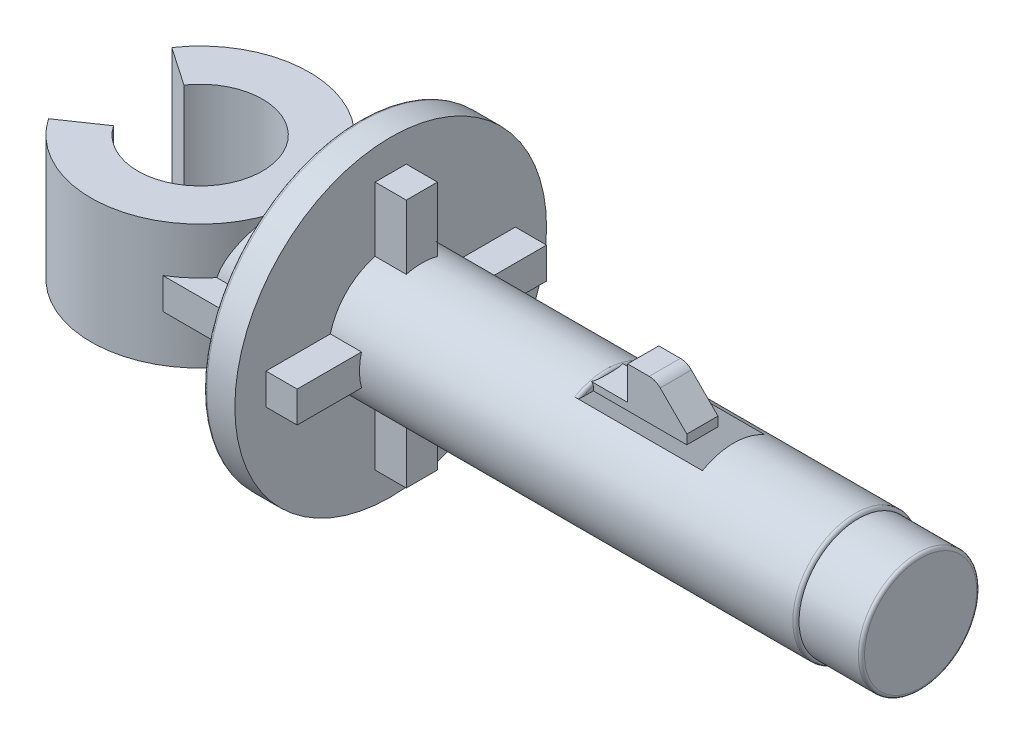
SolidWorks part; units mm, degrees
material "ABS PC"
ref_plane "Piano frontale" through (0, 0, 0) normal (0, 0, 1) x (1, 0, 0)
ref_plane "Piano superiore" through (0, 0, 0) normal (0, 1, 0) x (1, 0, 0)
ref_plane "Piano destro" through (0, 0, 0) normal (1, 0, 0) x (0, 0, -1)
sketch "Schizzo1" plane through (0, 0, 0) normal (1, 0, 0) x (0, 0, -1)
  circle A0 centre (0, 0) radius 2
  dimension "D1" = 4
extrude "Estrusione-Estrusione1" add sketch "Schizzo1" against normal blind 17
sketch "Schizzo2" plane through (0, 0, 0) normal (1, 0, 0) x (0, 0, -1)
  circle A0 centre (0, 0) radius 1.9
  dimension "D1" = 3.8
extrude "Taglio-Estrusione1" cut sketch "Schizzo2" against normal blind 2 flip side to cut
ref_plane "Piano1" through (0, -2, 0) normal (0, -1, 0) x (-1, 0, 0)
sketch "Schizzo6" plane through (0, -2, 0) normal (0, -1, 0) x (-1, 0, 0)
  line L1 (17, -2) -> (2, -2)
  line L2 (17, -2) -> (17, 2)
  line L3 (17, 2) -> (2, 2)
  line L4 (2, -2) -> (2, 2)
extrude "Taglio-Estrusione3" cut sketch "Schizzo6" against normal blind 0.1
ref_plane "Piano2" through (0, 2, 0) normal (0, 1, 0) x (1, 0, 0)
sketch "Schizzo5" plane through (0, 0, 0) normal (0, 1, 0) x (1, 0, 0)
  line L0 (-17, 2) -> (-17, -2) construction
  line L1 (-16, 1) -> (-3, 1)
  line L2 (-16, 1) -> (-16, -1)
  line L3 (-16, -1) -> (-3, -1)
  line L4 (-3, 1) -> (-3, -1)
  line L5 (-16, 1) -> (-3, -1) construction
  line L6 (-16, -1) -> (-3, 1) construction
  line L7 (-2, -2) -> (-2, 2) construction
  line L8 (-17, -2) -> (-2, -2) construction
  point P0 (-9.5, 0)
  dimension "D1" = 1
  dimension "D2" = 1
  dimension "D3" = 2
  dimension "D4" = 1
extrude "Taglio-Estrusione4" cut sketch "Schizzo5" against normal through all and the other way offset from surface 0.3 other way up to plane "Piano2"
sketch "Schizzo7" plane through (0, 2, 0) normal (0, 1, 0) x (1, 0, 0)
  line L0 (-10, 1) -> (-6, 1)
  line L1 (-6, 1) -> (-6, -1)
  line L2 (-6, -1) -> (-10, -1)
  line L9 (-2, 2) -> (-17, 2) construction
  line L10 (-17, -2) -> (-2, -2) construction
  line L11 (-10, 1) -> (-10, -1)
  line L12 (-2, -2) -> (-2, 2) construction
  dimension "D1" = 8
  dimension "D2" = 4
  dimension "D5" = 1
  dimension "D6" = 1
extrude "Taglio-Estrusione5" cut sketch "Schizzo7" against normal through all
ref_plane "Piano3" through (0, 1.7, 0) normal (0, 1, 0) x (1, 0, 0)
sketch "Schizzo12" plane through (0, 0, 0) normal (0, 0, 1) x (1, 0, 0)
  line L0 (-10, 2) -> (-8.9, 2)
  line L1 (-10, 1.7321) -> (-10, 2) construction
  line L2 (-8.9, 2) -> (-8.9, 3)
  line L3 (-8.9, 3) -> (-8, 3)
  line L4 (-8, 3) -> (-7, 2)
  line L5 (-7, 2) -> (-7, 1.7)
  line L6 (1.1, 1.7) -> (-1.1, 1.7) construction
  line L7 (-7, 1.7) -> (-10, 1.7)
  line L8 (-10, 1.7) -> (-10, 2)
  dimension "D1" = 3
  dimension "D2" = 1
  dimension "D3" = 0.3
  dimension "D4" = 0.9
  dimension "D5" = 45
  dimension "D6" = 0.3
extrude "Estrusione-Estrusione2" add sketch "Schizzo12" along normal mid plane 1
sketch "Schizzo16" plane through (0, 2, 0) normal (0, 1, 0) x (1, 0, 0)
  line L5 (-8.9, 0.5) -> (-10, 0.5)
  line L6 (-10, 0.5) -> (-10, 0)
  line L7 (-10, 0) -> (-10, -0.5)
  line L8 (-10, -0.5) -> (-8.9, -0.5)
  line L9 (-8.9, -0.5) -> (-8.9, 0.5)
  line L10 (-8.9, 0.5) -> (-10, 0.5)
  line L11 (-10, 0.5) -> (-10, 0)
  line L12 (-10, 0) -> (-10, -0.5)
  line L13 (-10, -0.5) -> (-8.9, -0.5)
  line L14 (-8.9, -0.5) -> (-8.9, 0.5)
  dimension "D1" = 0
extrude "Taglio-Estrusione6" cut sketch "Schizzo16" against normal blind 0.07
sketch "Schizzo17" plane through (0, 0, 0) normal (0, 0, 1) x (1, 0, 0)
  line L1 (-17, 4) -> (-16, 4)
  line L3 (-10, 2) -> (-17, 2) construction
  line L5 (0, 0) -> (-17, 0.05) construction
  line L6 (0, -2) -> (0, 2) construction
  line L7 (-17, 2) -> (-17, -1.9) construction
  line L8 (-17, 4) -> (-17, 0.05)
  line L9 (-16, 4) -> (-16, 0.0471)
  line L10 (-16, 0.0471) -> (-17, 0.05)
  dimension "D1" = 2
  dimension "D2" = 1
extrude "Estrusione-Estrusione4" add sketch "Schizzo17" along normal mid plane 1
mirror "Specchia2" about plane through (0, 0, 0) normal (0, 1, 0) of "Estrusione-Estrusione4"
sketch "Schizzo19" plane through (0, 0, 0) normal (0, 1, 0) x (1, 0, 0)
  line L0 (-17, 2) -> (-17, 0)
  line L2 (-17, 2) -> (-17, 4)
  line L3 (-17, 4) -> (-16, 4)
  line L4 (-16, 2) -> (-16, 4)
  line L5 (-17, 0) -> (-16, 0)
  line L6 (-16, 0) -> (-16, 2)
  dimension "D1" = 2
  dimension "D2" = 1
extrude "Estrusione-Estrusione5" add sketch "Schizzo19" along normal mid plane 1
mirror "Specchia5" about plane through (0, 0, 0) normal (0, 0, 1) of "Estrusione-Estrusione5"
sketch "Schizzo20" plane through (-17, 0, 0) normal (-1, 0, 0) x (0, 0, 1)
  line L0 (-5, 0) -> (5, 0) construction
  line L14 (1.9365, -0.5) -> (4, -0.5)
  line L15 (4, -0.5) -> (4, 0.5)
  line L16 (4, 0.5) -> (1.9365, 0.5)
  line L17 (0.5, 1.9365) -> (0.5, 4)
  line L18 (0.5, 4) -> (-0.5, 4)
  line L19 (-0.5, 4) -> (-0.5, 1.9365)
  line L20 (-1.9365, 0.5) -> (-4, 0.5)
  line L21 (-4, 0.5) -> (-4, -0.5)
  line L22 (-4, -0.5) -> (-1.9365, -0.5)
  line L23 (-0.6245, -1.9) -> (-0.5, -1.9)
  line L24 (-0.5, -1.9) -> (-0.5, -4)
  line L25 (-0.5, -4) -> (0.5, -4)
  line L26 (0.5, -4) -> (0.5, -1.9)
  line L27 (0.5, -1.9) -> (0.6245, -1.9)
  line L28 (1.9365, -0.5) -> (4, -0.5)
  line L29 (4, -0.5) -> (4, 0.5)
  line L30 (4, 0.5) -> (1.9365, 0.5)
  line L31 (0.5, 1.9365) -> (0.5, 4)
  line L32 (0.5, 4) -> (-0.5, 4)
  line L33 (-0.5, 4) -> (-0.5, 1.9365)
  line L34 (-1.9365, 0.5) -> (-4, 0.5)
  line L35 (-4, 0.5) -> (-4, -0.5)
  line L36 (-4, -0.5) -> (-1.9365, -0.5)
  line L37 (-0.6245, -1.9) -> (-0.5, -1.9)
  line L38 (-0.5, -1.9) -> (-0.5, -4)
  line L39 (-0.5, -4) -> (0.5, -4)
  line L40 (0.5, -4) -> (0.5, -1.9)
  line L41 (0.5, -1.9) -> (0.6245, -1.9)
  circle A0 centre (0, 0) radius 5
  arc A5 (0.6245, -1.9) -> (1.9365, -0.5) centre (0, 0) ccw
  arc A6 (1.9365, 0.5) -> (0.5, 1.9365) centre (0, 0) ccw
  arc A7 (-0.5, 1.9365) -> (-1.9365, 0.5) centre (0, 0) ccw
  arc A8 (-1.9365, -0.5) -> (-0.6245, -1.9) centre (0, 0) ccw
  arc A9 (0.6245, -1.9) -> (1.9365, -0.5) centre (0, 0) ccw
  arc A10 (1.9365, 0.5) -> (0.5, 1.9365) centre (0, 0) ccw
  arc A11 (-0.5, 1.9365) -> (-1.9365, 0.5) centre (0, 0) ccw
  arc A12 (-1.9365, -0.5) -> (-0.6245, -1.9) centre (0, 0) ccw
  point P3 (-4, 0)
  point P17 (0, 0)
  dimension "D1" = 1
  dimension "D2" = 0
extrude "Estrusione-Estrusione6" add sketch "Schizzo20" along normal blind 1 contours A0
sketch "Schizzo23" plane through (-18, 0, 0) normal (-1, 0, 0) x (0, 0, 1)
  circle A0 centre (0, 0) radius 2.25
  dimension "D1" = 4.5
extrude "Estrusione-Estrusione7" add sketch "Schizzo23" along normal blind 3
sketch "Schizzo22" plane through (0, 0, 0) normal (0, 1, 0) x (1, 0, 0)
  line L0 (-18, -5) -> (-28, -5) construction
  line L1 (-24.7623, -1.1299) -> (-26, -1.9773)
  line L2 (-24.7623, 1.1299) -> (-26, 1.9773)
  line L3 (-28.2241, 0) -> (0, 0) construction
  line L4 (0, -1.9) -> (0, 1.9) construction
  line L5 (-18, 5) -> (-18, -5) construction
  line L6 (-28.2241, -3.5) -> (-18, -3.5) construction
  line L7 (-28.2241, -3.5) -> (-28.2241, 3.5) construction
  line L8 (-28.2241, 3.5) -> (-18, 3.5) construction
  line L9 (-18, -3.5) -> (-18, 3.5) construction
  line L10 (-28.2241, -3.5) -> (-18, 3.5) construction
  line L11 (-28.2241, 3.5) -> (-18, -3.5) construction
  arc A0 (-24.7623, -1.1299) -> (-24.7623, 1.1299) centre (-23.112, 0) ccw
  arc A1 (-26, -1.9773) -> (-26, 1.9773) centre (-23.112, 0) ccw
  point P10 (-23.112, 0)
  dimension "D3" = 2
  dimension "D4" = 7
  dimension "D1" = 1.5
  dimension "D2" = 8
extrude "Estrusione-Estrusione10" add sketch "Schizzo22" along normal mid plane 4
sketch "Schizzo34" plane through (0, 0, 0) normal (0, 1, 0) x (1, 0, 0)
  line L1 (-18, 3) -> (-21.3093, 3)
  line L2 (-18, 3) -> (-18, 0)
  line L3 (-18, 5) -> (-18, -5) construction
  line L4 (-18, 0) -> (-21.3093, 3)
  arc A2 (-19.7673, 1.0308) -> (-26, 1.9773) centre (-23.112, 0) ccw construction
  dimension "D1" = 3
extrude "Estrusione-Estrusione8" add sketch "Schizzo34" along normal mid plane 1
mirror "Specchia6" about plane through (0, 0, 0) normal (0, 0, 1) of "Estrusione-Estrusione8"
ref_plane "Piano5" through (0, 2, 0) normal (0, 1, 0) x (1, 0, 0)
sketch "Schizzo35" plane through (0, 2, 0) normal (0, 1, 0) x (1, 0, 0)
  line L0 (-18, 2.1937) -> (-18, -2.1937) construction
  line L1 (-21, 1.0308) -> (-18, 1.0308)
  line L2 (-21, 1.0308) -> (-21, -1.0308)
  line L3 (-21, -1.0308) -> (-18, -1.0308)
  line L4 (-18, 1.0308) -> (-18, -1.0308)
  line L6 (-21, -1.0308) -> (-21, 1.0308) construction
  line L7 (-19.7673, 1.0308) -> (-21, 1.0308) construction
  line L8 (-21, -1.0308) -> (-19.7673, -1.0308) construction
extrude "Taglio-Estrusione7" cut sketch "Schizzo35" along normal blind 1
mirror "Specchia7" about plane through (0, 0, 0) normal (0, 1, 0) of "Taglio-Estrusione7"
fillet "Raccordo22" radius 0.5 1 edges at (-8, 3, 0)
fillet "Raccordo23" radius 0.1 1 edges at (-2, 2, 0)
fillet "Raccordo24" radius 0.1 1 edges at (0, 0, -1.9)
fillet "Raccordo25" radius 0.1 1 edges at (-18, 0, 5)
fillet "Raccordo28" radius 0.1 1 edges at (-10, 2, 0)
sketch "Schizzo36" plane through (-18, 0, 0) normal (-1, 0, 0) x (0, 0, 1)
  circle A1 centre (0, 0) radius 4.9
  circle A2 centre (0, 0) radius 4.9
  dimension "D1" = 0
extrude "Estrusione-Estrusione9" add sketch "Schizzo36" along normal blind 1 draft 80
